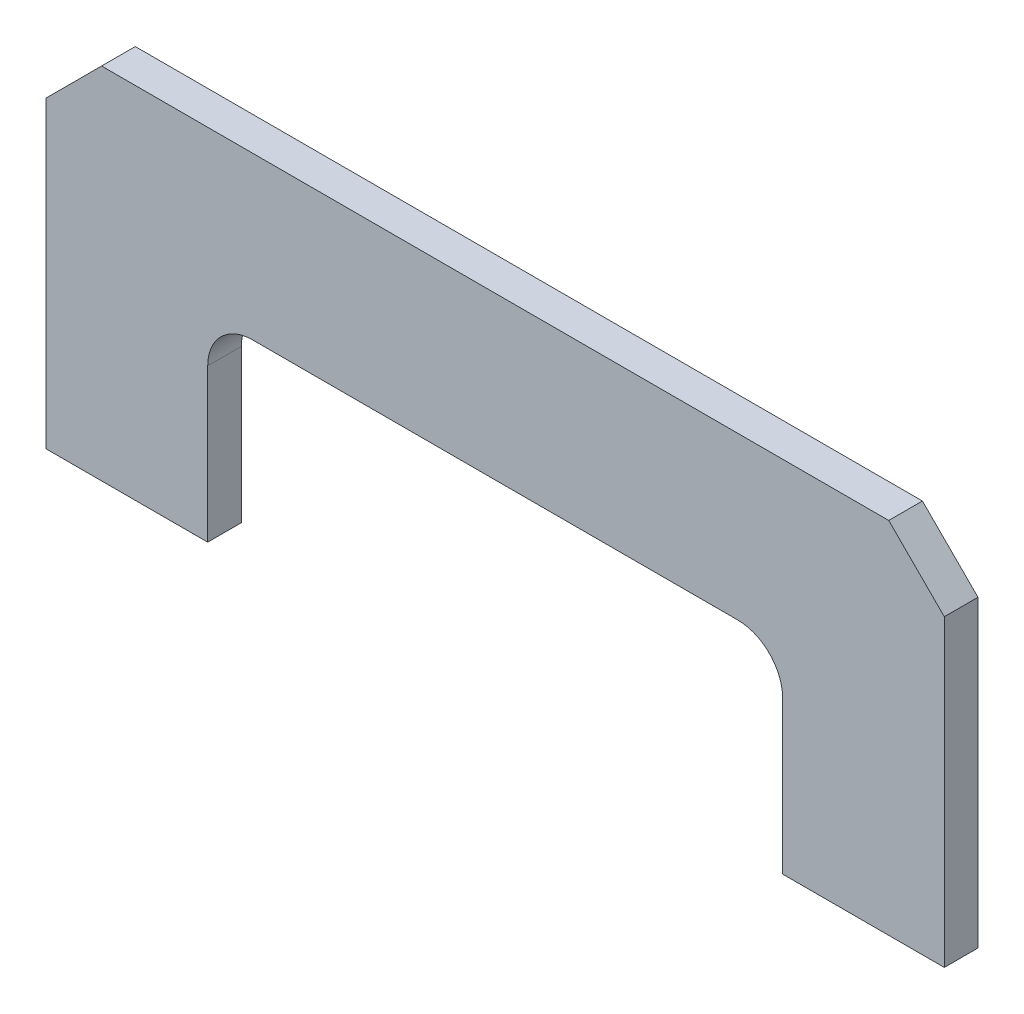
SolidWorks part; units mm, degrees
material "Alloy Steel"
ref_plane "Front Plane" through (0, 0, 0) normal (0, 0, 1) x (1, 0, 0)
ref_plane "Top Plane" through (0, 0, 0) normal (0, 1, 0) x (1, 0, 0)
ref_plane "Right Plane" through (0, 0, 0) normal (1, 0, 0) x (0, 0, -1)
sketch "Sketch1" plane through (0, 0, 0) normal (0, 0, 1) x (1, 0, 0)
  line L1 (0, 0) -> (11.43, 0)
  line L2 (0, 0) -> (0, 25.4)
  line L4 (11.43, 0) -> (11.43, 13.97)
  line L5 (52.07, 0) -> (63.5, 0)
  line L6 (52.07, 0) -> (52.07, 13.97)
  line L8 (63.5, 0) -> (63.5, 25.4)
  line L9 (11.43, 13.97) -> (52.07, 13.97)
  line L11 (0, 25.4) -> (63.5, 25.4)
  dimension "D1" = 40.64
  dimension "D3" = 63.5
  dimension "D4" = 25.4
  dimension "D5" = 11.43
extrude "Boss-Extrude1" add sketch "Sketch1" along normal blind 2.3813
fillet "Fillet1" radius 3.175 2 edges at (52.07, 13.97, 1.1906) (11.43, 13.97, 1.1906)
sketch "Sketch2" plane through (0, 0, 2.3813) normal (0, 0, 1) x (1, 0, 0)
  line L0 (0, 21.4711) -> (3.9289, 25.4)
  line L1 (0, 25.4) -> (0, 0) construction
  line L2 (63.5, 25.4) -> (0, 25.4) construction
  line L3 (59.5711, 25.4) -> (63.5, 21.4711)
  line L4 (63.5, 0) -> (63.5, 25.4) construction
  line M1 (0, 25.4) -> (0, 0)
  line M9 (63.5, 0) -> (63.5, 25.4)
  line M10 (63.5, 25.4) -> (0, 25.4)
  dimension "D1" = 45
  dimension "D2" = 45
  dimension "D3" = 5.5562
  dimension "D4" = 5.5562
extrude "Cut-Extrude1" cut sketch "Sketch2" against normal through all contours L0 M1 M10 | L3 M10 M9 region at (1.3096, 24.0904, 2.3813) region at (62.1904, 24.0904, 2.3813)
scale "Scale1" [suppressed]
